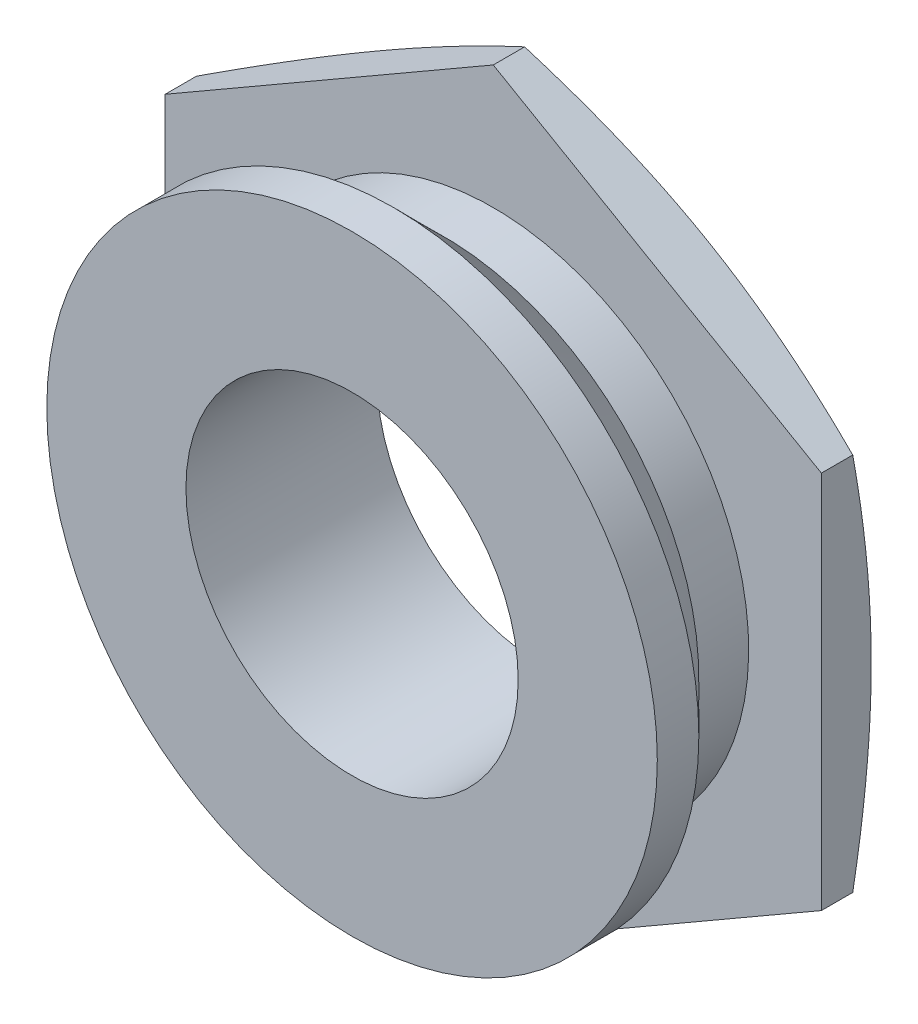
SolidWorks part; units mm, degrees
material "AISI 321 Annealed Stainless Steel (SS)"
ref_plane "Front Plane" through (0, 0, 0) normal (0, 0, 1) x (1, 0, 0)
ref_plane "Top Plane" through (0, 0, 0) normal (0, 1, 0) x (1, 0, 0)
ref_plane "Right Plane" through (0, 0, 0) normal (1, 0, 0) x (0, 0, -1)
sketch "Sketch1" plane through (0, 0, 0) normal (-1, 0, 0) x (0, 0, 1)
  line L0 (0, 0) -> (0, 3.075) construction
  line L1 (0, 3.075) -> (0.6, 3.075)
  line L6 (-0.6, 0) -> (-0.6, -3.95) construction
  line L7 (0.6, 3.075) -> (1.2, 3.675)
  line L8 (1.2, 3.675) -> (1.7, 3.675)
  line L9 (1.7, 3.675) -> (1.7, 0)
  line L10 (1.7, 0) -> (0, 0)
  line L11 (-0.6, -3.95) -> (0, -3.95) construction
  line L12 (0, -3.075) -> (0.6, -3.075) construction
  line L14 (0.6, -3.075) -> (1.2, -3.675) construction
  line L15 (1.2, -3.675) -> (1.7, -3.675) construction
  line L16 (1.7, -3.675) -> (1.7, 0) construction
  line L17 (0, -3.075) -> (0, 0) construction
  line L18 (0, 2) -> (1.7, 2) construction
  line L19 (0, -2) -> (1.7, -2) construction
  line L20 (0.85, 2) -> (0.85, -2) construction
  line L21 (1.7, 2) -> (2.3125, 2) construction
  line L22 (2.3125, 2) -> (2.05, 1.5453) construction
  line L23 (2.05, 1.5453) -> (1.9625, 1.5453) construction
  line L24 (1.9625, 1.5453) -> (1.7, 2) construction
  line L25 (2.0063, 2) -> (2.0063, 1.5453) construction
  line L26 (1.8313, 1.7727) -> (2.1813, 1.7727) construction
  line L27 (0, 3.075) -> (0, 3.95)
  line L28 (0, 3.95) -> (-0.6, 3.95)
  line L29 (-0.6, 3.95) -> (-0.6, 0)
  line L30 (-0.6, 0) -> (0, 0)
  line L31 (0, -3.95) -> (0, -3.075) construction
  point P23 (0.85, 0)
  point P24 (0.85, 0)
  point P33 (1, 0)
  dimension "D" = 0.5
  dimension "C" = 7.35
  dimension "MajorDiam" = 4
  dimension "D3" = 60
  dimension "Pitch" = 0.7
  dimension "D4" = 0.0875
  dimension "D5" = 0.35
  dimension "A" = 2.3
  dimension "HexThick" = 0.6
  dimension "HexWidth" = 7.9
  dimension "D2" = 0.6
  dimension "D1" = 0.6
revolve "Revolve1" add sketch "Sketch1" angle 360 about L10
sketch "Sketch3" plane through (0, 0, -0.6) normal (0, 0, -1) x (-1, 0, 0)
  line L7 (0, 4.5611) -> (-3.95, 2.2805)
  line L8 (-3.95, 2.2805) -> (-3.95, -2.2805)
  line L9 (-3.95, -2.2805) -> (0, -4.5611)
  line L10 (0, -4.5611) -> (3.95, -2.2805)
  line L11 (3.95, -2.2805) -> (3.95, 2.2805)
  line L12 (3.95, 2.2805) -> (0, 4.5611)
  circle A0 centre (0, 0) radius 3.95 construction
  circle A3 centre (0, 0) radius 2 construction
  circle A4 centre (0, 0) radius 3.95 construction
  dimension "D1" = 4
extrude "Boss-Extrude1" add sketch "Sketch3" against normal up to surface (0.6 mm away) up to face at (0, -3.95, 0)
sketch "Sketch10" plane through (0, 0, 0) normal (1, 0, 0) x (0, 0, -1)
  line L0 (0.3776, 4.5611) -> (0.6, 4.5611)
  line L2 (0.6, 4.5611) -> (0.6, 3.95)
  line L3 (0.6, 3.95) -> (0.6, 0) construction
  line L4 (0.6, 3.95) -> (0.3776, 4.5611)
  line L5 (0.6, -3.95) -> (0.6, 3.95) construction
  dimension "D1" = 20
revolve "Cut-Revolve4" cut sketch "Sketch10" angle 360 about L30
sketch "Sketch6" plane through (0, 0, 0) normal (1, 0, 0) x (0, 0, -1)
  line L1 (0.6, 0) -> (-1.7, 0)
  line L2 (0.6, 0) -> (0.6, 2)
  line L3 (0.6, 2) -> (-1.7, 2)
  line L4 (-1.7, 0) -> (-1.7, 2)
revolve "Cut-Revolve2" cut sketch "Sketch6" angle 360 about L30
sketch "Sketch7" plane through (0, 0, 1.7) normal (0, 0, 1) x (1, 0, 0)
  circle A0 centre (0, 0) radius 2
curve "Helix/Spiral1" pitch 0.7 height 3 turns 4.2857
sketch "Sketch8" [suppressed] plane through (0, 0, 0) normal (1, 0, 0) x (0, 0, -1)
  line L0 (-2.3125, 2) -> (-2.05, 1.5453) construction
  line L1 (-2.05, 1.5453) -> (-1.9625, 1.5453) construction
  line L2 (-1.9625, 1.5453) -> (-1.7, 2) construction
  line L3 (-1.7, 2) -> (-2.3125, 2) construction
  line L4 (-2.3125, 2) -> (-2.05, 1.5453)
  line L5 (-2.05, 1.5453) -> (-1.9625, 1.5453)
  line L6 (-1.9625, 1.5453) -> (-1.7, 2)
  line L7 (-1.7, 2) -> (-2.3125, 2)
sweep "Sweep1" [suppressed] add profiles "Sketch8" path "Helix/Spiral1"
sketch "Sketch12" [suppressed] plane through (0, 0, 1.7) normal (0, 0, 1) x (1, 0, 0)
  circle A0 centre (0, 0) radius 2 construction
  circle A1 centre (0, 0) radius 2
extrude "Cut-Extrude4" [suppressed] cut sketch "Sketch12" against normal blind 10 draft 70 and the other way blind 10 draft 45
sketch "Sketch13" [suppressed] plane through (0, 0, -0.6) normal (0, 0, -1) x (-1, 0, 0)
  circle A0 centre (0, 0) radius 2 construction
  circle A1 centre (0, 0) radius 2
extrude "Cut-Extrude5" [suppressed] cut sketch "Sketch13" against normal blind 10 draft 70 and the other way blind 10 draft 45
ref_plane "Contact Plane 1" through (0, 0, 1.7) normal (0, 0, 1) x (1, 0, 0)
ref_axis "Center Axis 1" through (0, 0, -0.1874) along (0, 0, 1)
equation "\"D4@Sketch1\"=\"Pitch@Sketch1\"*.125"
equation "\"D5@Sketch1\"=\"Pitch@Sketch1\"*.5"
equation "\"D4@Helix/Spiral1\"=\"Pitch@Sketch1\""
equation "\"D3@Helix/Spiral1\"=\"A@Sketch1\"+\"Pitch@Sketch1\""
equation "\"D2@Sketch1\"=\"HexThick@Sketch1\""
equation "\"D1@Sketch1\"=\"D2@Sketch1\""
equation "\"D1@Sketch3\"=\"MajorDiam@Sketch1\""
